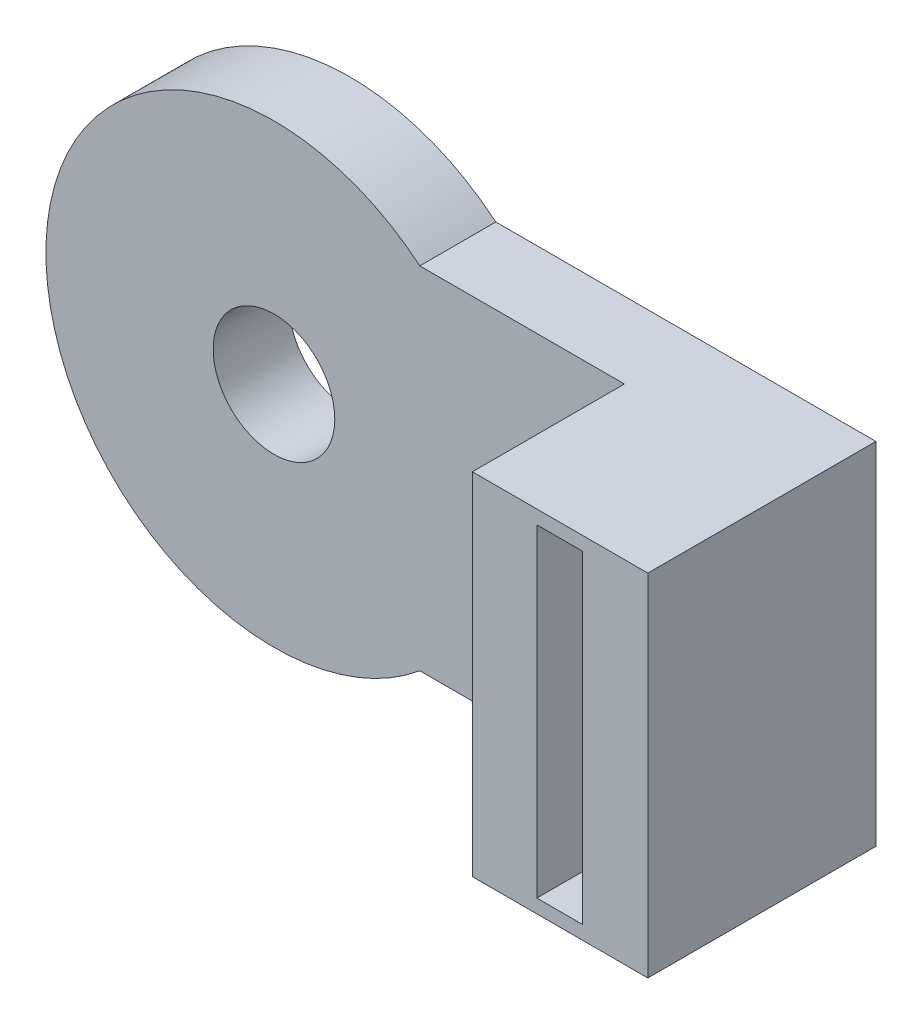
SolidWorks part; units mm, degrees
ref_plane "Piano frontale" through (0, 0, 0) normal (0, 0, 1) x (1, 0, 0)
ref_plane "Piano superiore" through (0, 0, 0) normal (0, 1, 0) x (1, 0, 0)
ref_plane "Piano destro" through (0, 0, 0) normal (1, 0, 0) x (0, 0, -1)
sketch "Schizzo1" plane through (0, 0, 0) normal (0, 0, 1) x (1, 0, 0)
  line L0 (9.5919, 11.5324) -> (34.5919, 11.5324) construction
  line L1 (9.5919, -11.5324) -> (34.5919, -11.5324)
  line L2 (34.5919, -11.5324) -> (34.5919, 11.5324)
  line L3 (34.5919, 11.5324) -> (9.5919, 11.5324)
  arc A0 (9.5919, 11.5324) -> (9.5919, -11.5324) centre (0, 0) ccw
  circle A1 centre (0, 0) radius 4
  dimension "D1" = 25
  dimension "D2" = 23.0648
extrude "Estrusione-Estrusione1" add sketch "Schizzo1" along normal mid plane 5
sketch "Schizzo2" plane through (0, 0, 2.5) normal (0, 0, 1) x (1, 0, 0)
  line L1 (23.0501, 11.5324) -> (34.5919, 11.5324)
  line L2 (23.0501, 11.5324) -> (23.0501, -11.5324)
  line L3 (23.0501, -11.5324) -> (34.5919, -11.5324)
  line L4 (34.5919, 11.5324) -> (34.5919, -11.5324)
  line L5 (23.0501, 11.5324) -> (34.5919, -11.5324) construction
  line L6 (23.0501, -11.5324) -> (34.5919, 11.5324) construction
  point P0 (28.821, 0)
extrude "Estrusione-Estrusione2" add sketch "Schizzo2" along normal blind 10
sketch "Schizzo3" plane through (0, 0, 12.5) normal (0, 0, 1) x (1, 0, 0)
  line L0 (34.5919, -11.5324) -> (34.5919, 11.5324) construction
  line L1 (27.2891, 10.63) -> (30.2891, 10.63)
  line L2 (27.2891, 10.63) -> (27.2891, -10.63)
  line L3 (27.2891, -10.63) -> (30.2891, -10.63)
  line L4 (30.2891, 10.63) -> (30.2891, -10.63)
  line L5 (27.2891, 10.63) -> (30.2891, -10.63) construction
  line L6 (27.2891, -10.63) -> (30.2891, 10.63) construction
  point P0 (28.7891, 0)
  dimension "D1" = 3
  dimension "D2" = 5.8028
  dimension "D3" = 21.26
extrude "Taglio-Estrusione1" cut sketch "Schizzo3" against normal blind 13
sketch "Schizzo4" plane through (0, 0, 2.5) normal (0, 0, 1) x (1, 0, 0)
  circle A0 centre (0, 0) radius 11.8718
